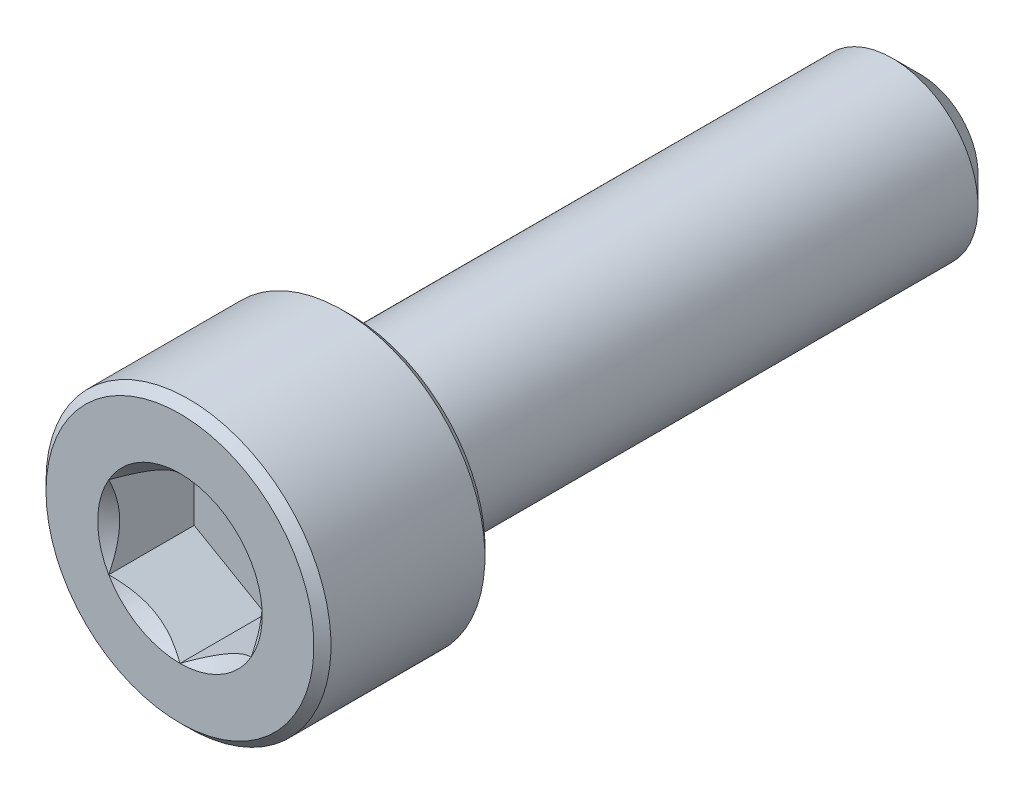
SolidWorks part; units mm, degrees
ref_plane "Front Plane" through (0, 0, 0) normal (0, 0, 1) x (1, 0, 0)
ref_plane "Top Plane" through (0, 0, 0) normal (0, 1, 0) x (1, 0, 0)
ref_plane "Right Plane" through (0, 0, 0) normal (1, 0, 0) x (0, 0, -1)
sketch "Sketch1" plane through (0, 0, 0) normal (1, 0, 0) x (0, 0, -1)
  line L0 (-13, 0) -> (13, 0) construction
  line L1 (13, 0) -> (13, 2) construction
  line L2 (13, 2) -> (12, 3) construction
  line L3 (12, 3) -> (-7, 3) construction
  line L5 (-7, 3) -> (-7, 5) construction
  line L6 (-7, 5) -> (-13, 5) construction
  line L7 (-13, 5) -> (-13, 0) construction
  line L8 (13, 2) -> (13, 3) construction
  line L9 (12.9375, 3.1083) -> (13.4375, 2.2422) construction
  line L10 (13.4375, 2.2422) -> (13.9375, 3.1083) construction
  line L11 (13.9375, 3.1083) -> (12.9375, 3.1083) construction
  line L12 (13.4375, 3.1083) -> (13.4375, 3) construction
  line L13 (13.4375, 2.2422) -> (13.4375, 2.3505) construction
  line L14 (13.375, 2.3505) -> (13.5, 2.3505) construction
  line L15 (13, 3) -> (13.875, 3) construction
  line L16 (12.9687, 3.0541) -> (13.9062, 3.0541) construction
  line L17 (13, 0) -> (13, -3) construction
  line L18 (-7.3, 5) -> (-7, 4.7) construction
  line L19 (-12.7, 5) -> (-13, 4.7) construction
  point P0 (-13, 2.5)
  point P3 (9.5, 3)
  point P4 (0, 0)
  point P22 (13.4375, 2.3505)
  point P24 (-7, 3)
  point P25 (13.4375, 3)
  point P28 (13.4375, 3.0541)
  point P29 (9.5, -3)
  point P31 (-10, 5)
  point P37 (-8.05, 5)
  point P38 (-12.55, 5)
  point P41 (-10, 0)
  dimension "head height" = 6
  dimension "D1" = 45
  dimension "Head Diameter" = 10
  dimension "Thread Size" = 6
  dimension "drive size" = 5
  dimension "Thread Pitch" = 1
  dimension "D2" = 0.125
  dimension "D3" = 1
  dimension "D4" = 3.5
  dimension "D7" = 0.3
  dimension "D8" = 0.3
  dimension "D9" = 0.3
  dimension "D10" = 0.15
  dimension "D11" = 0.75
  dimension "length" = 20
  dimension "Drive Depth" = 3
sketch "Sketch2" plane through (0, 0, 0) normal (1, 0, 0) x (0, 0, -1)
  line L1 (-12.7, 5) -> (-7.3, 5)
  line L4 (12, 3) -> (13, 2)
  line L5 (13, 2) -> (13, 0)
  line L6 (-7.3, 5) -> (-7, 4.7) construction
  line L7 (13, 0) -> (-13, 0)
  line L8 (-12.7, 5) -> (-13, 4.7) construction
  line L9 (-7.3, 5) -> (-7, 4.7)
  line L10 (-12.7, 5) -> (-13, 4.7)
  line L11 (-13, 4.7) -> (-13, 0)
  line L12 (-7, 4.7) -> (-7, 3)
  line L13 (-7, 3) -> (12, 3)
revolve "Revolve1" add sketch "Sketch2" angle 360 about L7
sketch "Sketch3" plane through (0, 0, 13) normal (0, 0, 1) x (1, 0, 0)
  line L1 (0, 2.8868) -> (-2.5, 1.4434)
  line L2 (-2.5, 1.4434) -> (-2.5, -1.4434)
  line L3 (-2.5, -1.4434) -> (0, -2.8868)
  line L4 (0, -2.8868) -> (2.5, -1.4434)
  line L5 (2.5, -1.4434) -> (2.5, 1.4434)
  line L6 (2.5, 1.4434) -> (0, 2.8868)
  circle A0 centre (0, 0) radius 2.5 construction
  dimension "D1" = 5
extrude "Cut-Extrude1" cut sketch "Sketch3" against normal up to vertex (3 mm away) up to point (0, 0, 10)
sketch "Sketch4" plane through (0, 0, 13) normal (0, 0, 1) x (1, 0, 0)
  circle A0 centre (0, 0) radius 2.8868
extrude "Cut-Extrude2" cut sketch "Sketch4" against normal blind 0.5 draft 45
ref_plane "Plane1" [suppressed] through (0, 0, 7) normal (0, 0, 1) x (1, 0, 0)
split "Split1" [suppressed] bodies to split 106
sketch "Sketch6" [suppressed] plane through (0, 0, -13) normal (0, 0, -1) x (-1, 0, 0)
  circle A0 centre (0, 0) radius 3
curve "Helix/Spiral1" [suppressed] pitch 1 height 21 turns 21
sketch "Sketch7" [suppressed] plane through (0, 0, 0) normal (1, 0, 0) x (0, 0, -1)
  line L0 (12.9687, 3.0541) -> (13.9062, 3.0541)
  line L1 (13.9062, 3.0541) -> (13.5, 2.3505)
  line L2 (13.5, 2.3505) -> (13.375, 2.3505)
  line L3 (13.375, 2.3505) -> (12.9687, 3.0541)
sweep "Cut-Sweep1" [suppressed] cut profiles "Sketch7" path "Helix/Spiral1"
sketch "Sketch8" [suppressed] plane through (0, 0, 7) normal (0, 0, -1) x (-1, 0, 0)
  circle A0 centre (0, 0) radius 3
extrude "Boss-Extrude1" [suppressed] add sketch "Sketch8" along normal through all draft 45
ref_plane "Plane2" [suppressed] through (0, 0, 10) normal (0, 0, 1) x (1, 0, 0)
sketch "Sketch9" [suppressed] plane through (0, 0, 10) normal (0, 0, 1) x (1, 0, 0)
  line L0 (0, 4.8625) -> (0.1309, 4.9983)
  line L1 (0, 4.8625) -> (-0.1309, 4.9983)
  line L2 (0, 5) -> (0, 0) construction
  line L3 (-0.1309, 4.9983) -> (0, 0) construction
  line L4 (0, 0) -> (0.1309, 4.9983) construction
  arc A0 (0.1309, 4.9983) -> (-0.1309, 4.9983) centre (0, 0) ccw
  circle A1 centre (0, 0) radius 4.8625 construction
  dimension "D2" = 9.725
  dimension "D3" = 3
extrude "Cut-Extrude4" [suppressed] cut sketch "Sketch9" against normal up to vertex and the other way up to vertex
pattern_circular "CirPattern2" [suppressed] count 96 over 360 about axis through (0, 0, 13) along (0, 0, -1) of bodies 113
equation "\"D2@Sketch1\" = \"Thread Pitch@Sketch1\" / 8"
equation "\"D3@Sketch1\" = \"Thread Pitch@Sketch1\""
equation "\"D3@Helix/Spiral1\" = \"length@Sketch1\" + \"Thread Pitch@Sketch1\""
equation "\"D4@Helix/Spiral1\" = \"Thread Pitch@Sketch1\""
equation "\"D4@Sketch1\" = \"Thread Pitch@Sketch1\" * 3.5"
equation "\"D7@Sketch1\"=\"head height@Sketch1\"*.05"
equation "\"D8@Sketch1\"=\"D7@Sketch1\""
equation "\"D9@Sketch1\"=\"D7@Sketch1\""
equation "\"D10@Sketch1\"=\"D7@Sketch1\"/2"
equation "\"D11@Sketch1\"=\"D10@Sketch1\"*5"
equation "\"D1@CirPattern2\"=( 360 / \"D3@Sketch9\" )*0.8"
equation "\"D1@Sketch3\" = \"drive size@Sketch1\""
equation "\"D2@Sketch9\"=\"Head Diameter@Sketch1\" * 0.9725"
